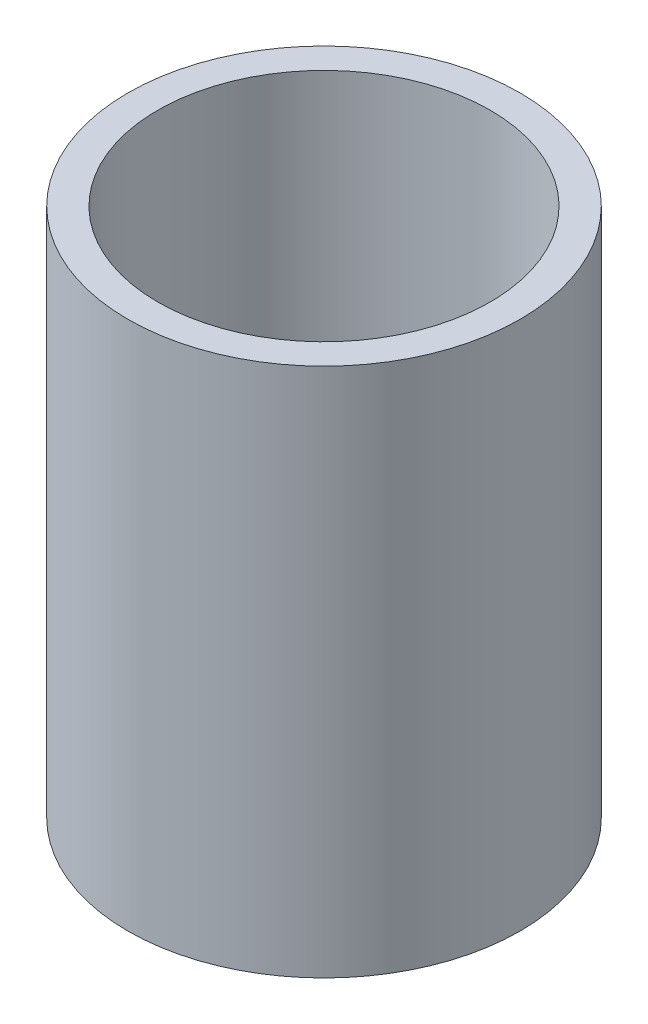
SolidWorks part; units mm, degrees
ref_plane "Front Plane" through (0, 0, 0) normal (0, 0, 1) x (1, 0, 0)
ref_plane "Top Plane" through (0, 0, 0) normal (0, 1, 0) x (1, 0, 0)
ref_plane "Right Plane" through (0, 0, 0) normal (1, 0, 0) x (0, 0, -1)
sketch "Sketch1" plane through (0, 0, 0) normal (0, 1, 0) x (1, 0, 0)
  circle A0 centre (0, 0) radius 35
  dimension "SLEEVE_OD" = 70
extrude "Boss-Extrude1" add sketch "Sketch1" along normal blind 94.5751
sketch "Sketch2" plane through (0, 0, 0) normal (0, 1, 0) x (1, 0, 0)
  circle A0 centre (0, 0) radius 29.6682
  dimension "BORE_D" = 59.3364
extrude "Cut-Extrude1" cut sketch "Sketch2" along normal through all
chamfer "Chamfer1" distance 3.9941 angle 45 rebuild error yes
